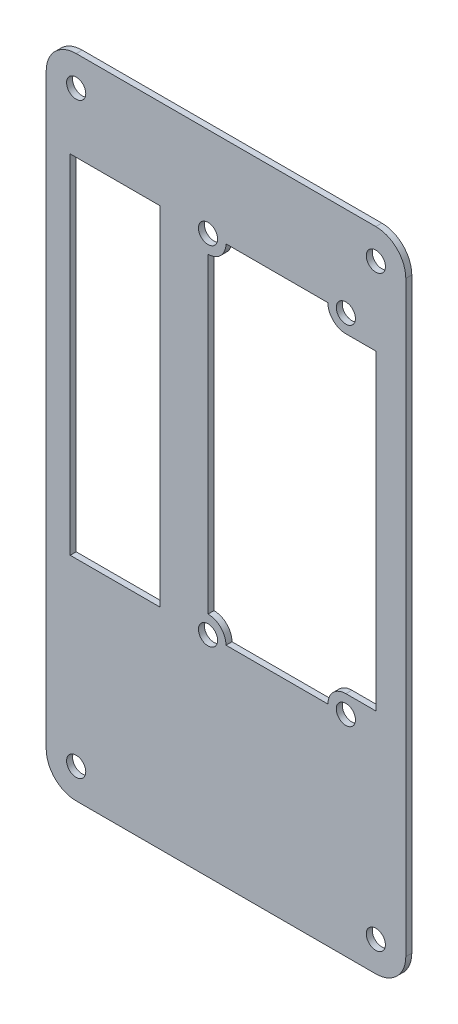
SolidWorks part; units mm, degrees
ref_plane "正面" through (0, 0, 0) normal (0, 0, 1) x (1, 0, 0)
ref_plane "平面" through (0, 0, 0) normal (0, 1, 0) x (1, 0, 0)
ref_plane "右側面" through (0, 0, 0) normal (1, 0, 0) x (0, 0, -1)
sketch "ｽｹｯﾁ1" plane through (0, 0, 0) normal (0, 0, 1) x (1, 0, 0)
  line L1 (-30, 54) -> (30, 54)
  line L2 (-30, 54) -> (-30, -54)
  line L3 (-30, -54) -> (30, -54)
  line L4 (30, 54) -> (30, -54)
  line L5 (-30, 54) -> (30, -54) construction
  line L6 (-30, -54) -> (30, 54) construction
  point P0 (0, 0)
  dimension "D1" = 108
  dimension "D2" = 60
extrude "ﾎﾞｽ - 押し出し1" add sketch "ｽｹｯﾁ1" along normal blind 1
sketch "ｽｹｯﾁ2" plane through (0, 0, 1) normal (0, 0, 1) x (1, 0, 0)
  line L0 (30, -54) -> (30, 54) construction
  line L1 (-3, 39) -> (20, 39) construction
  line L2 (-3, 39) -> (-3, -19) construction
  line L3 (-3, -19) -> (20, -19) construction
  line L4 (20, 39) -> (20, -19) construction
  line L5 (30, 54) -> (-30, 54) construction
  circle A0 centre (-3, 39) radius 1.6
  circle A1 centre (20, 39) radius 1.6
  circle A2 centre (-3, -19) radius 1.6
  circle A3 centre (20, -19) radius 1.6
  dimension "D5" = 3.2
  dimension "D6" = 3.2
  dimension "D7" = 3.2
  dimension "D8" = 3.2
  dimension "D1" = 58
  dimension "D2" = 23
  dimension "D3" = 10
  dimension "D4" = 15
extrude "ｶｯﾄ - 押し出し1" cut sketch "ｽｹｯﾁ2" against normal blind 5
sketch "ｽｹｯﾁ3" plane through (0, 0, 1) normal (0, 0, 1) x (1, 0, 0)
  line L1 (-3, 39) -> (20, 39)
  line L2 (-3, 39) -> (-3, -19)
  line L3 (-3, -19) -> (20, -19)
  line L4 (20, 39) -> (20, -19)
  circle A0 centre (-3, 39) radius 3
  circle A1 centre (20, 39) radius 3
  circle A2 centre (-3, -19) radius 3
  circle A3 centre (20, -19) radius 3
  dimension "D1" = 6
  dimension "D2" = 6
  dimension "D3" = 6
  dimension "D4" = 6
extrude "ｶｯﾄ - 押し出し2" cut sketch "ｽｹｯﾁ3" against normal blind 5 contours A3 L4 A1 L1 A0 L2 A2 L3 region at (8.5, 10, 1)
sketch "ｽｹｯﾁ4" plane through (0, 0, 1) normal (0, 0, 1) x (1, 0, 0)
  line L0 (30, -54) -> (30, 54) construction
  line L1 (-25, -49) -> (25, -49) construction
  line L2 (-25, -49) -> (-25, 49) construction
  line L3 (-25, 49) -> (25, 49) construction
  line L4 (25, -49) -> (25, 49) construction
  line L5 (-25, -49) -> (25, 49) construction
  line L6 (-25, 49) -> (25, -49) construction
  line L8 (30, 54) -> (-30, 54) construction
  circle A0 centre (-25, 49) radius 1.6
  circle A1 centre (25, 49) radius 1.6
  circle A2 centre (-25, -49) radius 1.6
  circle A3 centre (25, -49) radius 1.6
  point P0 (0, 0)
  dimension "D3" = 3.2
  dimension "D4" = 3.2
  dimension "D5" = 3.2
  dimension "D6" = 3.2
  dimension "D1" = 5
  dimension "D2" = 5
extrude "ｶｯﾄ - 押し出し3" cut sketch "ｽｹｯﾁ4" against normal blind 5
sketch "ｽｹｯﾁ5" plane through (0, 0, 1) normal (0, 0, 1) x (1, 0, 0)
  line L1 (20, 36) -> (25, 36)
  line L2 (20, 36) -> (20, -16)
  line L3 (20, -16) -> (25, -16)
  line L4 (25, 36) -> (25, -16)
  dimension "D1" = 5
  dimension "D2" = 52
extrude "ｶｯﾄ - 押し出し4" cut sketch "ｽｹｯﾁ5" against normal blind 10
sketch "ｽｹｯﾁ6" plane through (0, 0, 1) normal (0, 0, 1) x (1, 0, 0)
  line L0 (-3, 36) -> (-3, -16) construction
  line L1 (-26, 39) -> (-11, 39)
  line L2 (-26, 39) -> (-26, -19)
  line L3 (-26, -19) -> (-11, -19)
  line L4 (-11, 39) -> (-11, -19)
  line L5 (0, 39) -> (17, 39) construction
  line L6 (0, -19) -> (17, -19) construction
  dimension "D1" = 15
  dimension "D2" = 8
  dimension "D3" = 0
  dimension "D4" = 0
extrude "ｶｯﾄ - 押し出し5" cut sketch "ｽｹｯﾁ6" against normal blind 10
fillet "ﾌｨﾚｯﾄ1" radius 5 4 edges at (30, -54, 0.5) (-30, -54, 0.5) (-30, 54, 0.5) (30, 54, 0.5)
